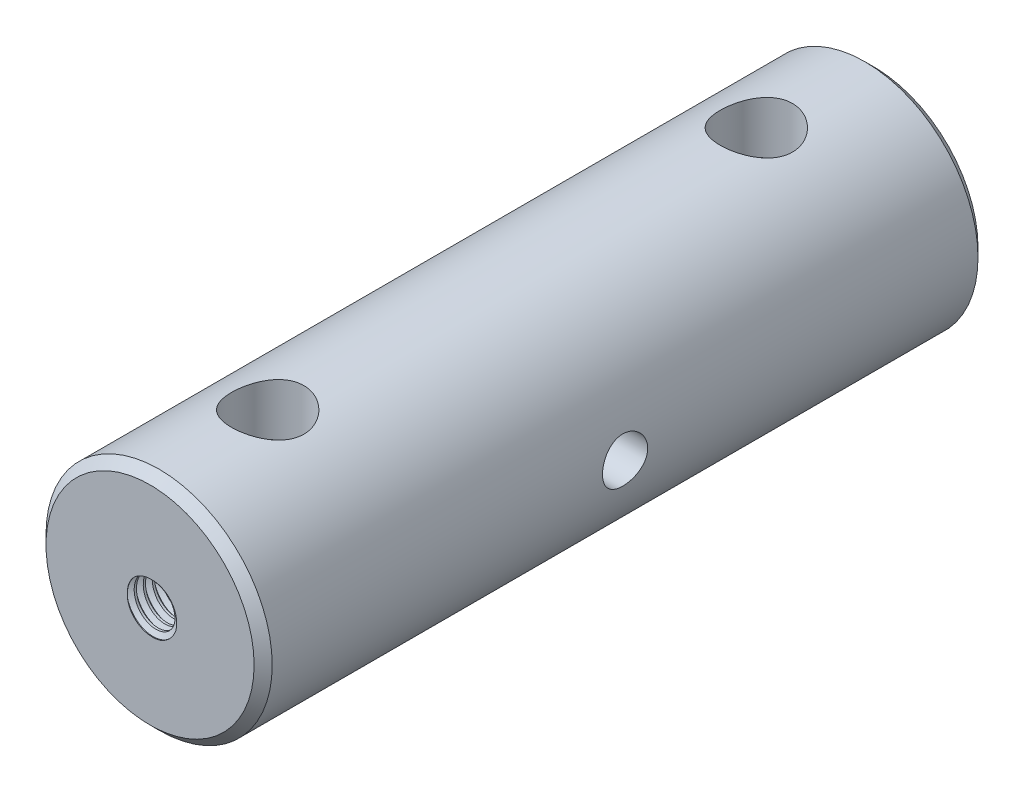
SolidWorks part; units mm, degrees
material "AISI 1020"
ref_plane "Front Plane" through (0, 0, 0) normal (0, 0, 1) x (1, 0, 0)
ref_plane "Top Plane" through (0, 0, 0) normal (0, 1, 0) x (1, 0, 0)
ref_plane "Right Plane" through (0, 0, 0) normal (1, 0, 0) x (0, 0, -1)
sketch "Sketch1" plane through (0, 0, 0) normal (0, 0, 1) x (1, 0, 0)
  circle A0 centre (0, 0) radius 12.5
  dimension "D1" = 25
extrude "Boss-Extrude1" add sketch "Sketch1" along normal blind 80
ref_plane "Plane1" through (0, 12.5, 0) normal (0, 1, 0) x (1, 0, 0)
sketch "Sketch2" plane through (0, 12.5, 0) normal (0, 1, 0) x (1, 0, 0)
  line L0 (0, 0) -> (0, -80) construction
  line L1 (-12.5, -80) -> (12.5, -80) construction
  circle A0 centre (0, -13) radius 4
  circle A1 centre (0, -67) radius 4
  dimension "D1" = 8
  dimension "D2" = 13
  dimension "D3" = 13
extrude "Cut-Extrude1" cut sketch "Sketch2" against normal blind 6
sketch "Sketch3" plane through (0, 0, 80) normal (0, 0, 1) x (1, 0, 0)
  circle A0 centre (0, 0) radius 2.5
  dimension "D1" = 5
extrude "Cut-Extrude2" cut sketch "Sketch3" against normal blind 50
sketch "Sketch4" plane through (0, 0, 0) normal (1, 0, 0) x (0, 0, -1)
  line L0 (-80, 0) -> (0, 0) construction
  line L1 (-80, 12.5) -> (-80, -12.5) construction
  circle A0 centre (-40, 0) radius 2.5
  dimension "D2" = 5
  dimension "D1" = 40
extrude "Cut-Extrude3" cut sketch "Sketch4" against normal blind 14 from offset 12.5
chamfer "Chamfer1" distance 1 angle 45 2 edges at (12.5, 0, 0) (12.5, 0, 80)
thread "Thread1" pitch 1 method cut profile "Thread Profile1" start angle 0, offset 2, length 10, pitch 1, diameter 5
ref_plane "Plane2" through (-2.5, 0, 82) normal (0, -1, 0) x (-1, 0, 0)
sketch "Thread Profile1" plane through (-2.5, 0, 82) normal (0, -1, 0) x (-1, 0, 0)
  line L0 (0, 0) -> (0, 1) construction
  line L1 (0, 0) -> (0.5413, 0.3125)
  line L2 (0.5413, 0.3125) -> (0.5413, 0.4375)
  line L3 (0.5413, 0.4375) -> (0, 0.75)
  line L4 (0.5413, 0.375) -> (0, 0.375) construction
  line L11 (0, 0) -> (0, 0.75)
  point P2 (0, 0)
  dimension "Pitch" = 1
  dimension "Profile_Angle" = 60
  dimension "Profile_Land" = 0.125
  dimension "Profile_Height" = 0.5413
